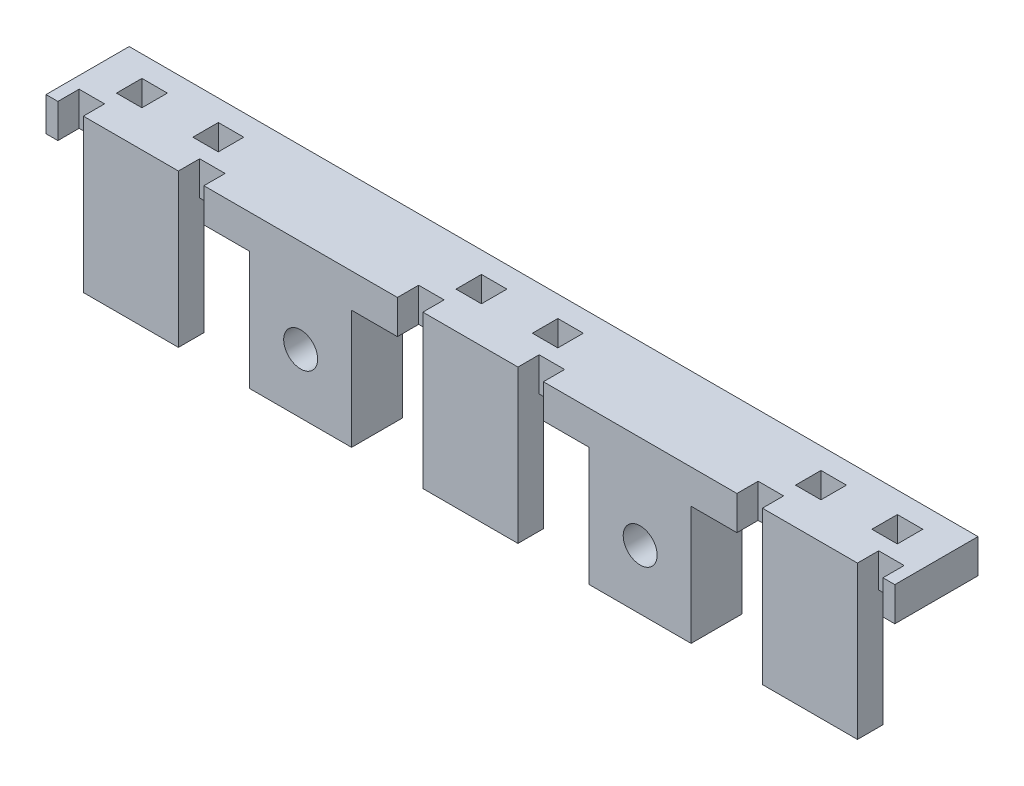
SolidWorks part; units mm, degrees
ref_plane "前视基准面" through (0, 0, 0) normal (0, 0, 1) x (1, 0, 0)
ref_plane "上视基准面" through (0, 0, 0) normal (0, 1, 0) x (1, 0, 0)
ref_plane "右视基准面" through (0, 0, 0) normal (1, 0, 0) x (0, 0, -1)
other "Configuration Table"
sketch "草图1" plane through (0, 0, 0) normal (0, 1, 0) x (1, 0, 0)
  line L1 (0, 0) -> (117.5679, 0)
  line L2 (0, 0) -> (0, -35.2117)
  line L3 (0, -35.2117) -> (117.5679, -35.2117)
  line L4 (117.5679, 0) -> (117.5679, -35.2117)
extrude "凸台-拉伸1" add sketch "草图1" along normal blind 2
sketch "草图3" plane through (0, 2, 0) normal (0, 1, 0) x (1, 0, 0)
  line L0 (117.5679, 0) -> (0, 0) construction
  line L1 (2.2, -3.65) -> (0.7, -3.65)
  line L2 (2.2, -3.65) -> (2.2, -5.15)
  line L3 (2.2, -5.15) -> (0.7, -5.15)
  line L4 (0.7, -3.65) -> (0.7, -5.15)
  line L5 (3.5, -2) -> (6.5, -2) construction
  line L6 (7.8, -3.65) -> (9.3, -3.65)
  line L7 (7.8, -3.65) -> (7.8, -5.15)
  line L8 (7.8, -5.15) -> (9.3, -5.15)
  line L9 (9.3, -3.65) -> (9.3, -5.15)
  line L10 (2, -1.25) -> (3.5, -1.25)
  line L11 (2, -1.25) -> (2, -2.75)
  line L12 (2, -2.75) -> (3.5, -2.75)
  line L13 (3.5, -1.25) -> (3.5, -2.75)
  line L14 (6.5, -1.25) -> (8, -1.25)
  line L15 (6.5, -1.25) -> (6.5, -2.75)
  line L16 (6.5, -2.75) -> (8, -2.75)
  line L17 (8, -1.25) -> (8, -2.75)
  line L18 (2.2, -4.4) -> (7.8, -4.4) construction
  line L19 (5, -2) -> (5, -4.4) construction
  line L20 (0, 0) -> (0, -35.2117) construction
  dimension "D1" = 5.6
  dimension "D2" = 1.5
  dimension "D3" = 1.5
  dimension "D4" = 1.5
  dimension "D5" = 1.5
  dimension "D6" = 2.4
  dimension "D7" = 3
  dimension "D8" = 2
  dimension "D9" = 5
extrude "切除-拉伸1" cut sketch "草图3" against normal through all
pattern_linear "阵列(线性)1" count 3 spacing 20 along (1, 0, 0) of "切除-拉伸1"
sketch "草图4" plane through (0, 0, 0) normal (0, -1, 0) x (1, 0, 0)
  line L0 (117.5679, 0) -> (0, 0) construction
  line L1 (0, 0) -> (50, 0)
  line L2 (0, 0) -> (0, 4.9)
  line L3 (0, 4.9) -> (50, 4.9)
  line L4 (50, 0) -> (50, 4.9)
  line L5 (0, 0) -> (0, 35.2117) construction
  dimension "D1" = 4.9
  dimension "D2" = 50
extrude "切除-拉伸2" cut sketch "草图4" against normal through all flip side to cut
sketch "草图5" plane through (0, 0, 0) normal (0, -1, 0) x (1, 0, 0)
  line L0 (50, 4.9) -> (49.3, 4.9) construction
  line L1 (42.2, 4.9) -> (47.8, 4.9)
  line L2 (42.2, 4.9) -> (42.2, 3.4)
  line L3 (42.2, 3.4) -> (47.8, 3.4)
  line L4 (47.8, 4.9) -> (47.8, 3.4)
  line L5 (42.2, 4.9) -> (42.2, 3.65) construction
  line L6 (47.8, 3.65) -> (47.8, 4.9) construction
  line L7 (2.2, 4.9) -> (2.2, 3.65) construction
  line L8 (22.2, 4.9) -> (27.8, 4.9)
  line L9 (22.2, 4.9) -> (22.2, 3.4)
  line L10 (22.2, 3.4) -> (27.8, 3.4)
  line L11 (27.8, 4.9) -> (27.8, 3.4)
  line L12 (2.2, 4.9) -> (7.8, 4.9)
  line L13 (2.2, 4.9) -> (2.2, 3.4)
  line L14 (2.2, 3.4) -> (7.8, 3.4)
  line L15 (7.8, 4.9) -> (7.8, 3.4)
  line L16 (7.8, 3.65) -> (7.8, 4.9) construction
  line L17 (22.2, 4.9) -> (22.2, 3.65) construction
  line L18 (27.8, 3.65) -> (27.8, 4.9) construction
  line L19 (7.8, 3.4) -> (12, 3.4) construction
  line L20 (12, 4.9) -> (18, 4.9)
  line L21 (12, 4.9) -> (12, 3.4)
  line L22 (12, 3.4) -> (18, 3.4)
  line L23 (18, 4.9) -> (18, 3.4)
  line L24 (32, 4.9) -> (38, 4.9)
  line L25 (32, 4.9) -> (32, 3.4)
  line L26 (32, 3.4) -> (38, 3.4)
  line L27 (38, 4.9) -> (38, 3.4)
  line L28 (18, 3.4) -> (22.2, 3.4) construction
  line L29 (27.8, 3.4) -> (32, 3.4) construction
  line L30 (38, 3.4) -> (42.2, 3.4) construction
  dimension "D1" = 1.5
  dimension "D2" = 6
extrude "凸台-拉伸2" add sketch "草图5" along normal blind 7
sketch "草图6" plane through (0, 0, 3.4) normal (0, 0, -1) x (-1, 0, 0)
  line L0 (-38, -3.5) -> (-32, -3.5) construction
  line L1 (-38, -7) -> (-38, 0) construction
  line L2 (-32, -7) -> (-32, 0) construction
  line L3 (-18, -3.5) -> (-12, -3.5) construction
  line L4 (-18, -7) -> (-18, 0) construction
  line L5 (-12, -7) -> (-12, 0) construction
  circle A0 centre (-35, -3.5) radius 2
  circle A1 centre (-35, -3.5) radius 1
  circle A2 centre (-15, -3.5) radius 2
  circle A3 centre (-15, -3.5) radius 1
  dimension "D1" = 2
  dimension "D2" = 4
extrude "切除-拉伸4" cut sketch "草图6" against normal through all contours A1 | A3
sketch "草图7" plane through (0, 0, 3.4) normal (0, 0, -1) x (-1, 0, 0)
  line L0 (-32, 0) -> (-38, 0) construction
  line L1 (-38, 0) -> (-38, -7) construction
  line L2 (-38, -7) -> (-32, -7) construction
  line L3 (-32, -7) -> (-32, 0) construction
  line L4 (-12, 0) -> (-18, 0) construction
  line L5 (-18, 0) -> (-18, -7) construction
  line L6 (-18, -7) -> (-12, -7) construction
  line L7 (-12, -7) -> (-12, 0) construction
  line L8 (-32, 0) -> (-38, 0)
  line L9 (-38, 0) -> (-38, -7)
  line L10 (-38, -7) -> (-32, -7)
  line L11 (-32, -7) -> (-32, 0)
  line L12 (-12, 0) -> (-18, 0)
  line L13 (-18, 0) -> (-18, -7)
  line L14 (-18, -7) -> (-12, -7)
  line L15 (-12, -7) -> (-12, 0)
  circle A0 centre (-15, -3.5) radius 1 construction
  circle A1 centre (-35, -3.5) radius 1 construction
  circle A2 centre (-15, -3.5) radius 1
  circle A3 centre (-35, -3.5) radius 1
extrude "凸台-拉伸3" add sketch "草图7" along normal blind 1.5
